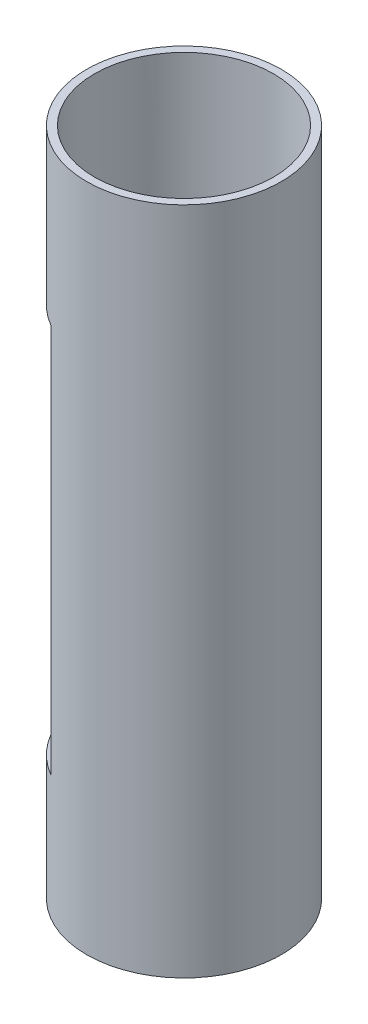
SolidWorks part; units mm, degrees
material "ПВХ 0.007 Смягченный"
ref_plane "Спереди" through (0, 0, 0) normal (0, 0, 1) x (1, 0, 0)
ref_plane "Сверху" through (0, 0, 0) normal (0, 1, 0) x (1, 0, 0)
ref_plane "Справа" through (0, 0, 0) normal (1, 0, 0) x (0, 0, -1)
sketch "Эскиз1" plane through (0, 0, 0) normal (0, 1, 0) x (1, 0, 0)
  circle A0 centre (0, 0) radius 25
  circle A1 centre (0, 0) radius 23
  dimension "ExDBody" = 50
  dimension "InDBody" = 46
extrude "Бобышка-Вытянуть1" add sketch "Эскиз1" along normal blind 172
ref_plane "Плоскость1" through (0, 32, 0) normal (0, -1, 0) x (-1, 0, 0)
sketch "Эскиз2" plane through (0, 32, 0) normal (0, -1, 0) x (-1, 0, 0)
  line L0 (0, 0) -> (29.6146, 51.294)
  line L1 (29.6146, 51.294) -> (33.4528, -57.9419)
  line L2 (33.4528, -57.9419) -> (0, 0)
  line L3 (-50, 0) -> (50, 0) construction
  dimension "D1" = 120
  dimension "D2" = 60
extrude "Вырез-Вытянуть1" cut sketch "Эскиз2" against normal blind 100
